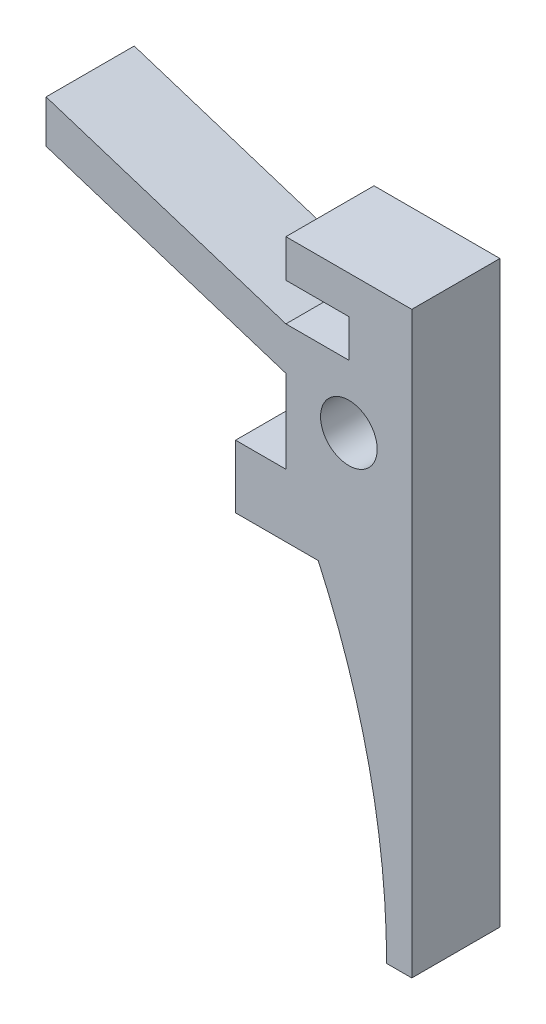
SolidWorks part; units mm, degrees
ref_plane "Alzado" through (0, 0, 0) normal (0, 0, 1) x (1, 0, 0)
ref_plane "Planta" through (0, 0, 0) normal (0, 1, 0) x (1, 0, 0)
ref_plane "Vista lateral" through (0, 0, 0) normal (1, 0, 0) x (0, 0, -1)
sketch "Croquis1" plane through (0, 0, 0) normal (0, 0, 1) x (1, 0, 0)
  line L1 (-5, 5) -> (5, 5)
  line L2 (-5, 1.5989) -> (-5, -5)
  line L4 (5, 5) -> (5, -5)
  line L5 (-5, 5) -> (5, -5) construction
  line L6 (-5, -5) -> (5, 5) construction
  line L7 (3, -35) -> (5, -35)
  line L10 (5, -35) -> (5, -5)
  line L11 (3, -35) -> (5, -5) construction
  line L12 (4, -20) -> (5, -35) construction
  line L13 (-1, -20) -> (-57.25, -35) construction
  line L14 (-57.25, -35) -> (3, -35) construction
  line L25 (-24.0497, 7.6907) -> (-24.0497, 11.0918)
  line L26 (-5, 1.5989) -> (-24.0497, 7.6907)
  line L28 (-5, 5) -> (-24.0497, 11.0918)
  line L29 (-2.4315, -10) -> (-9, -10)
  line L32 (-5, -5) -> (-9, -5)
  line L33 (-9, -10) -> (-9, -5)
  line L34 (-4.5293, -10) -> (3, -35) construction
  line L35 (5, -5.9639) -> (4.9344, -5.984) construction
  arc A0 (3, -35) -> (-2.4315, -10) centre (-57.25, -35) ccw
  circle A1 centre (0, 0) radius 2.25
  point P0 (0, 0)
  point P6 (4, -20)
  point P14 (-15.6355, 3.6315)
  point P15 (0, -7.5)
  dimension "D5" = 4.5
  dimension "D1" = 10
  dimension "D2" = 10
  dimension "D3" = 30
  dimension "D4" = 2
  dimension "D6" = 20
  dimension "D7" = 20
  dimension "D8" = 4
  dimension "D9" = 5
extrude "Saliente-Extruir1" add sketch "Croquis1" along normal blind 7
sketch "Croquis5" plane through (0, 5, 0) normal (0, 1, 0) x (1, 0, 0)
  line L0 (0, -3.5) -> (5, -3.5) construction
  line L2 (5, -7) -> (5, 0) construction
  line L4 (0, -7) -> (5, -7)
  line L5 (0, -7) -> (0, 0)
  line L6 (0, 0) -> (5, 0)
  line L7 (5, -7) -> (5, 0)
  line L8 (0, -7) -> (5, 0) construction
  line L9 (0, 0) -> (5, -7) construction
  point P6 (2.5, -3.5)
  dimension "D1" = 5
  dimension "D2" = 7
extrude "Saliente-Extruir3" add sketch "Croquis5" along normal blind 3
sketch "Croquis6" plane through (0, 8, 0) normal (0, 1, 0) x (1, 0, 0)
  line L0 (0, 0) -> (0, -7) construction
  line L1 (-5, -7) -> (5, -7)
  line L2 (-5, -7) -> (-5, 0)
  line L3 (-5, 0) -> (5, 0)
  line L4 (5, -7) -> (5, 0)
  line L5 (-5, -7) -> (5, 0) construction
  line L6 (-5, 0) -> (5, -7) construction
  point P0 (0, -3.5)
extrude "Saliente-Extruir4" add sketch "Croquis6" along normal blind 3
